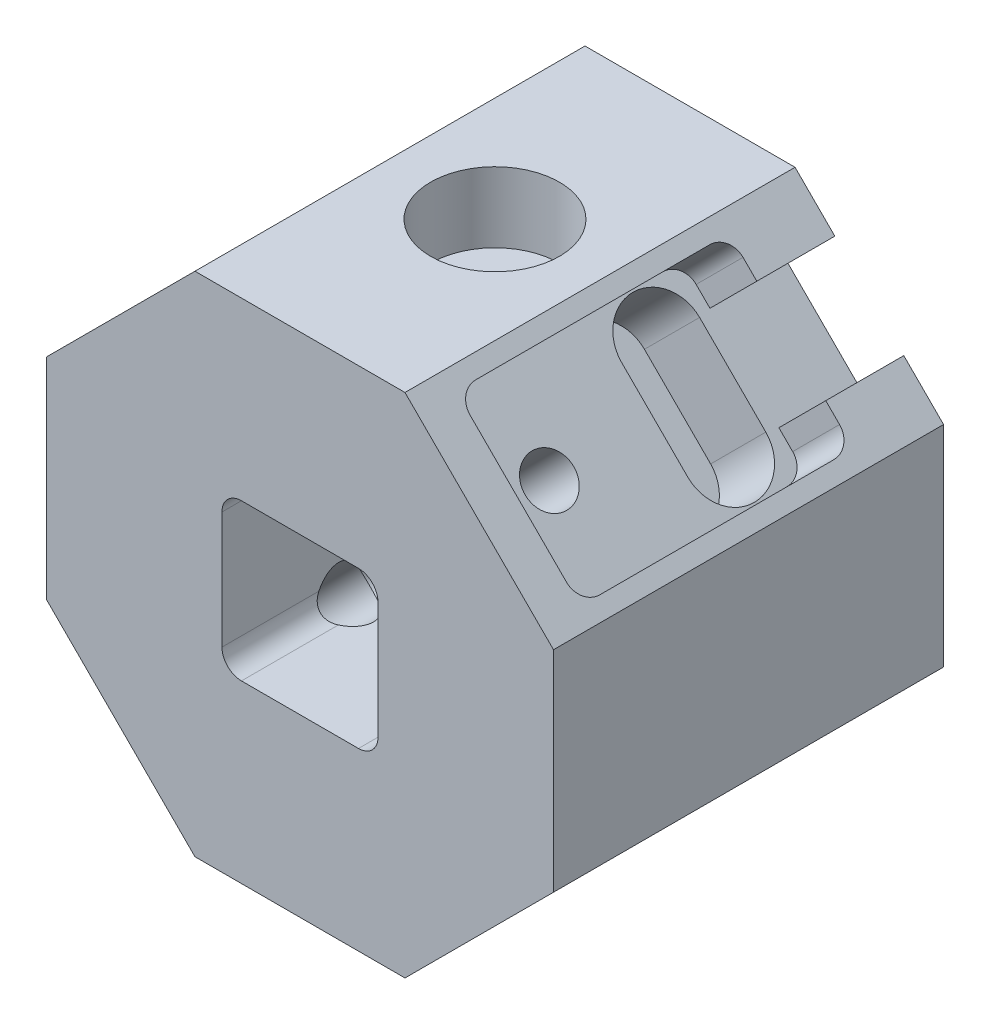
SolidWorks part; units mm, degrees
material "AISI 304"
ref_plane "Front Plane" through (0, 0, 0) normal (0, 0, 1) x (1, 0, 0)
ref_plane "Top Plane" through (0, 0, 0) normal (0, 1, 0) x (1, 0, 0)
ref_plane "Right Plane" through (0, 0, 0) normal (1, 0, 0) x (0, 0, -1)
sketch "Sketch1" plane through (0, 0, 0) normal (0, 0, 1) x (1, 0, 0)
  line L1 (-2, -2) -> (2, -2)
  line L2 (-2, -2) -> (-2, 2)
  line L3 (-2, 2) -> (2, 2)
  line L4 (2, -2) -> (2, 2)
  line L5 (-2, -2) -> (2, 2) construction
  line L6 (-2, 2) -> (2, -2) construction
  line L7 (-2.6924, 6.5) -> (-6.5, 2.6924)
  line L8 (-6.5, 2.6924) -> (-6.5, -2.6924)
  line L9 (-6.5, -2.6924) -> (-2.6924, -6.5)
  line L10 (-2.6924, -6.5) -> (2.6924, -6.5)
  line L11 (2.6924, -6.5) -> (6.5, -2.6924)
  line L12 (6.5, -2.6924) -> (6.5, 2.6924)
  line L13 (6.5, 2.6924) -> (2.6924, 6.5)
  line L14 (2.6924, 6.5) -> (-2.6924, 6.5)
  circle A1 centre (0, 0) radius 6.5 construction
  point P0 (0, 0)
  dimension "D2" = 13
  dimension "D1" = 4
extrude "Boss-Extrude1" add sketch "Sketch1" along normal blind 10
fillet "Fillet2" radius 0.5 4 edges at (-2, -2, 5) (2, -2, 5) (2, 2, 5) (-2, 2, 5)
ref_axis "Axis1" through (0, 0, 10.5) along (0, 0, -1)
sketch "Sketch11" plane through (4.5962, 4.5962, 0) normal (0.7071, 0.7071, 0) x (0, 0, -1)
  line L0 (0, -2.6924) -> (0, 2.6924) construction
  line L1 (-9, 2.25) -> (-2, 2.25)
  line L2 (-9, 2.25) -> (-9, -2.25)
  line L3 (-9, -2.25) -> (-2, -2.25)
  line L4 (-2, 2.25) -> (-2, -2.25)
  line L5 (-9, 1.25) -> (0, 1.25)
  line L6 (-9, 1.25) -> (-9, -1.25)
  line L7 (-9, -1.25) -> (0, -1.25)
  line L8 (0, 1.25) -> (0, -1.25)
  line L9 (-10, 0) -> (0, 0) construction
  line L10 (-10, -2.6924) -> (-10, 2.6924) construction
  line M10 (0, -2.6924) -> (0, 2.6924)
  dimension "D1" = 1
  dimension "D2" = 4.5
  dimension "D3" = 7
  dimension "D4" = 2.5
extrude "Cut-Extrude3" cut sketch "Sketch11" against normal blind 1.7 contours L2 L5 L4 L1 | L2 L9 L4 L5 | L9 L6 L7 L4 | L7 L2 L3 L4 | L4 L9 L8 L5 | L9 L4 L7 M10 region at (3.3588, 5.8336, 5.5) region at (4.1543, 5.0381, 5.5) region at (4.1543, 5.0381, 1) region at (5.0381, 4.1543, 5.5) region at (5.0381, 4.1543, 1) region at (5.8336, 3.3588, 5.5)
fillet "Fillet3" radius 0.5 4 edges at (5.5861, 2.4042, 9) (5.5861, 2.4042, 2) (2.4042, 5.5861, 2) (2.4042, 5.5861, 9)
sketch "Sketch12" plane through (3.3941, 3.3941, 0) normal (0.7071, 0.7071, 0) x (0, 0, -1)
  line L0 (-7, 0) -> (0, 0) construction
  line L1 (-9, 1.75) -> (-9, -1.75) construction
  point P0 (-7, 0)
  dimension "D1" = 2
hole_wizard "Tap Drill for M1.6 Tap2" positions "3DSketch8" profile "Sketch13" hole size "M1.6" standard "GB"
sketch3d "3DSketch8"
  point P0 (3.3941, 3.3941, 7)
sketch "Sketch13" plane through (3.3941, 3.3941, 7) normal (0, 0, 1) x (-0.7071, 0.7071, 0)
  line L0 (0, 0) -> (0, 5.3755)
  line L1 (0, 5.3755) -> (0.625, 5)
  line L2 (0.625, 5) -> (0.625, 0)
  line L5 (0.625, 0) -> (0, 0)
  line L10 (0, 5.3755) -> (-0.625, 5) construction
  line L11 (0, -6.35) -> (0, 107.95) construction
  dimension "Hole Dia." = 1.25
  dimension "Hole Depth" = 5
  dimension "Drill Angle" = 118
sketch "Sketch14" plane through (3.3941, 3.3941, 0) normal (0.7071, 0.7071, 0) x (0, 0, -1)
  line L0 (-3.3, 1.2) -> (-3.3, -1.2) construction
  line L1 (-2.3, 1.2) -> (-2.3, -1.2)
  line L2 (-4.3, 1.2) -> (-4.3, -1.2)
  line L3 (-7, 0) -> (0, 0) construction
  line L4 (-2, 1.75) -> (-2, 1.25) construction
  arc A0 (-2.3, 1.2) -> (-4.3, 1.2) centre (-3.3, 1.2) ccw
  arc A1 (-4.3, -1.2) -> (-2.3, -1.2) centre (-3.3, -1.2) ccw
  point P4 (-3.3, 0)
  dimension "D1" = 1
  dimension "D2" = 1.3
  dimension "D3" = 2.4
extrude "Cut-Extrude4" cut sketch "Sketch14" against normal blind 2
pattern_circular "CirPattern14" count 4 over 360 about axis through (0, 0, 10.5) along (0, 0, -1) of "Cut-Extrude3", "Fillet3", "Tap Drill for M1.6 Tap2", "Cut-Extrude4"
sketch "Sketch4" plane through (0, 6.5, 0) normal (0, 1, 0) x (1, 0, 0)
  line L0 (0, 0) -> (0, -10) construction
  line L1 (2.6924, 0) -> (-2.6924, 0) construction
  line L2 (2.6924, -10) -> (-2.6924, -10) construction
  point P0 (0, -5)
  point P1 (0, -5)
hole_wizard "CBORE for M1.6 Hexagon socket head cap screws1" positions "3DSketch5" profile "Sketch7" counterbore size "M1.6" standard "GB" end condition through all
sketch3d "3DSketch5"
  point P0 (0, 6.5, 5)
sketch "Sketch7" plane through (0, 6.5, 5) normal (1, 0, 0) x (0, 0, 1)
  line L0 (0, 0) -> (0, 13)
  line L1 (0, 13) -> (0.9, 13)
  line L3 (0.9, 13) -> (0.9, 1.8)
  line L4 (0.9, 1.8) -> (1.65, 1.8)
  line L5 (1.65, 1.8) -> (1.65, 0)
  line L7 (1.65, 0) -> (0, 0)
  line L11 (0, -6.35) -> (0, 107.95) construction
  dimension "Thru Hole Dia." = 1.8
  dimension "Thru Hole Depth" = 13
  dimension "C'Bore Dia." = 3.3
  dimension "C'Bore Depth" = 1.8
